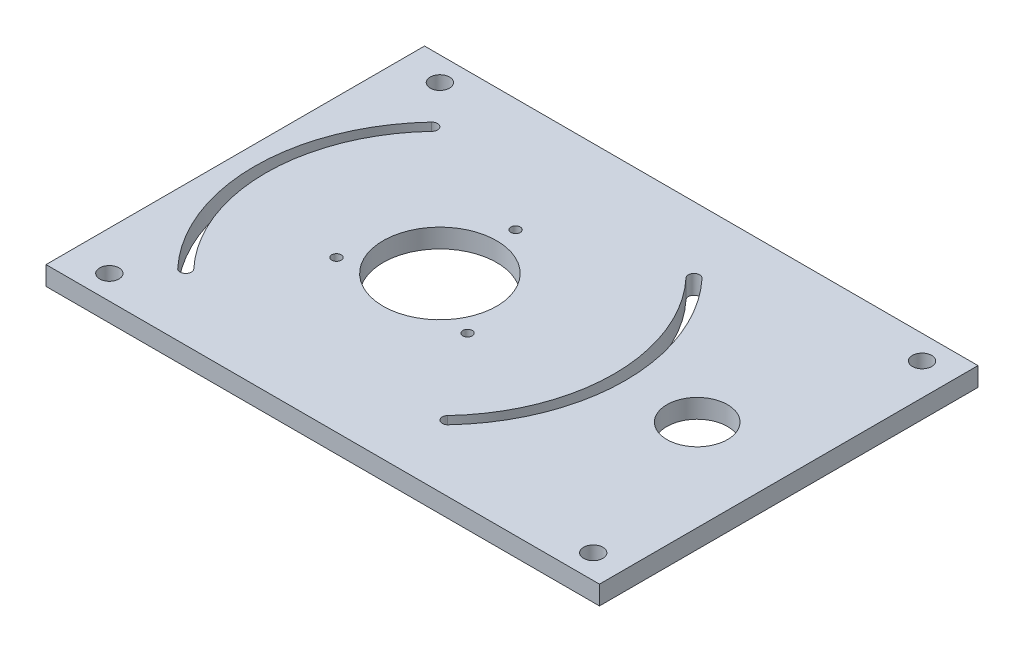
SolidWorks part; units mm, degrees
note: The reader was unsure of these and kept them because the rebuilt part matched: shared geometry of "Sketch1<4>".
material "1060 Alloy"
ref_plane "Front Plane" through (0, 0, 0) normal (0, 0, 1) x (1, 0, 0)
ref_plane "Top Plane" through (0, 0, 0) normal (0, 1, 0) x (1, 0, 0)
ref_plane "Right Plane" through (0, 0, 0) normal (1, 0, 0) x (0, 0, -1)
sketch "Sketch1" plane through (0, 0, 0) normal (0, 1, 0) x (1, 0, 0)
  line L0 (54.0555, -70) -> (92.1555, -70)
  line L1 (92.1555, -70) -> (92.1555, 30)
  line L2 (92.1555, 30) -> (54.0555, 30)
  line L3 (-25.5137, -53.3624) -> (-25.5137, -50.8067)
  line L4 (-25.5137, -50.8067) -> (-25.5137, 10.8067) construction
  line L5 (0, -56.703) -> (0, -3.871) construction
  line L6 (-9.906, -30.287) -> (9.906, -30.287) construction
  line L7 (0, -3.871) -> (0, -10.2787) construction
  line L8 (-9.906, -20) -> (9.906, -20) construction
  line L9 (14.7387, -10.2787) -> (-14.7387, -10.2787) construction
  line L10 (-50, -70) -> (-46.4645, -66.4645)
  line L11 (-50, -70) -> (50, -70)
  line L12 (-25.5137, 10.8067) -> (-25.5137, 13.3624)
  line L13 (-50, 30) -> (50, 30)
  line L14 (32.5269, 12.5269) -> (34.6482, 14.6482)
  line L15 (-50, -70) -> (50, 30) construction
  line L16 (-50, 30) -> (50, -70) construction
  line L17 (-50, -70) -> (-40, -70)
  line L18 (-40, -70) -> (-40, -66.4645)
  line L19 (-40, -66.4645) -> (-46.4645, -66.4645)
  line L20 (-50, -70) -> (-50, -60)
  line L21 (-50, -60) -> (-46.4645, -60)
  line L22 (-46.4645, -60) -> (-46.4645, -66.4645)
  line L23 (-50, 30) -> (-50, 20)
  line L24 (-50, 20) -> (-46.4645, 20)
  line L25 (-46.4645, 20) -> (-46.4645, 26.4645)
  line L26 (-46.4645, 26.4645) -> (-40, 26.4645)
  line L27 (-40, 26.4645) -> (-40, 30)
  line L28 (50, -70) -> (54.0555, -70)
  line L29 (54.0555, -70) -> (54.0555, 30)
  line L30 (50, 30) -> (50, 20)
  line L31 (50, 20) -> (46.4645, 20)
  line L32 (46.4645, 20) -> (46.4645, 26.4645)
  line L33 (46.4645, 26.4645) -> (40, 26.4645)
  line L34 (40, 26.4645) -> (40, 30)
  line L35 (54.0555, 30) -> (50, 30)
  line L36 (46, -20) -> (49, -20) construction
  line L37 (46.4645, -60) -> (46.4645, -66.4645)
  line L38 (50, -60) -> (46.4645, -60)
  line L39 (50, -70) -> (50, -60)
  line L40 (40, -66.4645) -> (46.4645, -66.4645)
  line L41 (40, -70) -> (40, -66.4645)
  line L42 (50, -70) -> (40, -70)
  line L43 (50, -70) -> (46.4645, -66.4645)
  line L44 (32.5269, -52.5269) -> (34.6482, -54.6482)
  line L45 (-32.5269, 12.5269) -> (-34.6482, 14.6482)
  line L46 (-54.0555, 30) -> (-50, 30)
  line L47 (-54.0555, -70) -> (-54.0555, 30)
  line L48 (-50, -70) -> (-54.0555, -70)
  line L49 (-32.5269, -52.5269) -> (-34.6482, -54.6482)
  line L50 (25.5137, -53.3624) -> (25.5137, -50.8067)
  line L51 (25.5137, 10.8067) -> (25.5137, 13.3624)
  line L52 (68, -20.02) -> (0, -20) construction
  circle A0 centre (68, -20.02) radius 8
  circle A3 centre (0, -20) radius 40
  circle A5 centre (0, -20) radius 15
  circle A6 centre (0, -20) radius 41.95
  arc A7 (46, -20) -> (32.5269, 12.5269) centre (0, -20) ccw
  arc A8 (34.6482, -54.6482) -> (34.6482, 14.6482) centre (0, -20) ccw
  circle A9 centre (34.6315, 12.5102) radius 1.5
  circle A10 centre (34.6315, -52.5102) radius 1.5
  arc A11 (46, -20) -> (32.5269, -52.5269) centre (0, -20) cw
  circle A12 centre (-34.6315, 12.5102) radius 1.5
  arc A13 (-46, -20) -> (-32.5269, 12.5269) centre (0, -20) cw
  circle A14 centre (-34.6315, -52.5102) radius 1.5
  arc A15 (-46, -20) -> (-32.5269, -52.5269) centre (0, -20) ccw
  arc A16 (-34.6482, -54.6482) -> (-34.6482, 14.6482) centre (0, -20) cw
  circle A17 centre (-17.3128, -30.0169) radius 1.25
  circle A18 centre (17.3192, -30.0091) radius 1.25
  circle A19 centre (0.001, -0.0052) radius 1.25
  point P2 (0, -20)
  point P8 (0, -30.287)
  point P25 (0, -10.2787)
  point P34 (43.6629, -63.6629)
  point P56 (43.6629, 23.6629)
  point P57 (-43.6629, 23.6629)
  point P58 (-43.6629, -63.6629)
  point P59 (0, -20)
  dimension "D1" = 4
extrude "Boss-Extrude1" add sketch "Sketch1" along normal blind 5
extrude "Boss-Extrude4" add sketch "Sketch1<4>" against normal blind 11 separate body
sketch "Sketch1<4>" plane through (0, 0, 0) normal (0, 1, 0) x (1, 0, 0) same geometry as "Sketch1"
hole_wizard "Tap Drill for 1/4-20 Tap1" positions "Sketch2" profile "Sketch3" hole size "1/4-20" standard "ANSI Inch"
sketch "Sketch2" plane through (0, 0, 0) normal (0, -1, 0) x (-1, 0, 0)
  point P3 (43.6629, -63.6629)
  point P6 (43.6629, 23.6629)
  point P13 (-83.7109, 23.6629)
  point P15 (-84.1709, -63.6629)
sketch "Sketch3" plane through (-43.6629, 0, 63.6629) normal (1, 0, 0) x (0, 0, -1)
  line L0 (0, 0) -> (0, 26.9338)
  line L1 (0, 26.9338) -> (2.5527, 25.4)
  line L2 (2.5527, 25.4) -> (2.5527, 0)
  line L5 (2.5527, 0) -> (0, 0)
  line L10 (0, 26.9338) -> (-2.5527, 25.4) construction
  line L11 (0, -6.35) -> (0, 107.95) construction
  dimension "Hole Dia." = 5.1054
  dimension "Hole Depth" = 25.4
  dimension "Drill Angle" = 118
